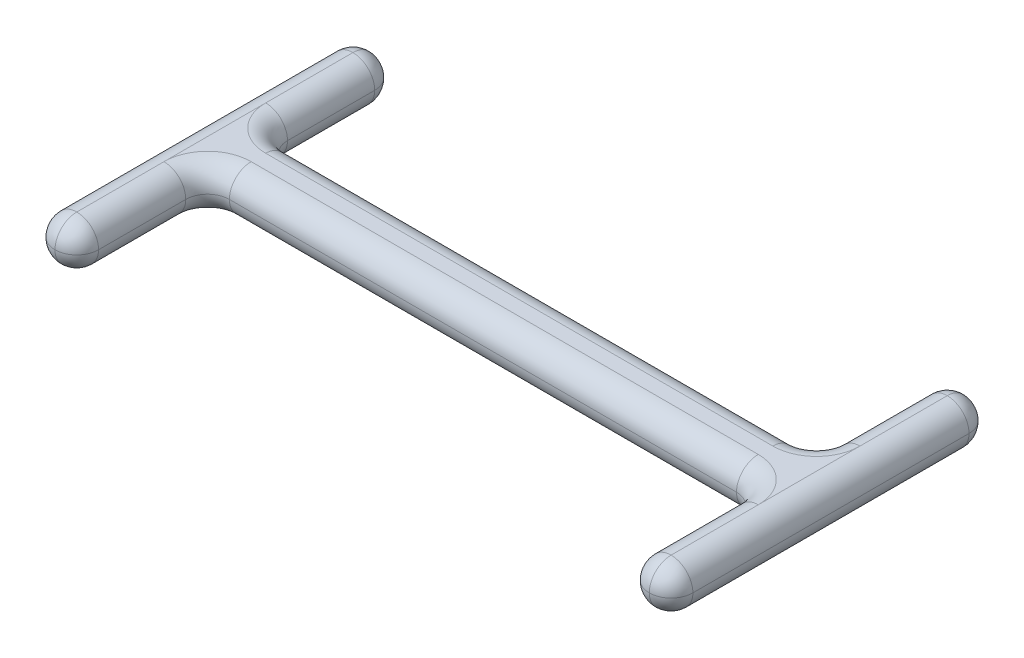
SolidWorks part; units mm, degrees
ref_plane "Front Plane" through (0, 0, 0) normal (0, 0, 1) x (1, 0, 0)
ref_plane "Top Plane" through (0, 0, 0) normal (0, 1, 0) x (1, 0, 0)
ref_plane "Right Plane" through (0, 0, 0) normal (1, 0, 0) x (0, 0, -1)
sketch "Sketch2" plane through (0, 0, 0) normal (0, 1, 0) x (1, 0, 0)
  line L0 (-54.865, 27.5) -> (-54.865, -27.5)
  line L1 (-54.865, -27.5) -> (-47.365, -27.5)
  line L2 (-47.365, -27.5) -> (-47.365, -5)
  line L3 (-47.365, -5) -> (47.365, -5)
  line L6 (0, 21.8993) -> (0, 0) construction
  line L7 (-48.8931, 0) -> (-54.865, 0) construction
  line L8 (47.365, -27.5) -> (47.365, -5)
  line L9 (54.865, -27.5) -> (47.365, -27.5)
  line L10 (54.865, 27.5) -> (54.865, -27.5)
  line L11 (-47.365, 27.5) -> (-47.365, 5)
  line L12 (-54.865, 27.5) -> (-47.365, 27.5)
  line L13 (54.865, 27.5) -> (47.365, 27.5)
  line L14 (47.365, 27.5) -> (47.365, 5)
  line L15 (-47.365, 5) -> (47.365, 5)
  dimension "D1" = 55
  dimension "D2" = 94.73
  dimension "D3" = 7.5
  dimension "D4" = 10
extrude "Boss-Extrude1" add sketch "Sketch2" along normal blind 7.5
fillet "Fillet1" radius 3.75 24 edges at (0, 7.5, 5) (0, 0, 5) (0, 7.5, -5) (0, 0, -5) (-47.365, 3.75, 27.5) (-47.365, 7.5, 16.25) (-47.365, 0, 16.25) (-54.865, 3.75, -27.5) (-54.865, 7.5, 0) (-54.865, 3.75, 27.5) (-54.865, 0, 0) (-47.365, 7.5, -16.25) (-47.365, 3.75, -27.5) (-47.365, 0, -16.25) (47.365, 7.5, 16.25) (47.365, 3.75, 27.5) (47.365, 0, 16.25) (47.365, 3.75, -27.5) (47.365, 7.5, -16.25) (47.365, 0, -16.25) (54.865, 3.75, 27.5) (54.865, 7.5, 0) (54.865, 3.75, -27.5) (54.865, 0, 0)
fillet "Fillet2" radius 3.75 16 edges at (-48.4633, 6.4017, -26.4017) (-48.4633, 1.0983, -26.4017) (-53.7667, 6.4017, 26.4017) (-53.7667, 1.0983, 26.4017) (48.4633, 1.0983, 26.4017) (48.4633, 6.4017, 26.4017) (53.7667, 1.0983, -26.4017) (53.7667, 6.4017, -26.4017) (-53.7667, 6.4017, -26.4017) (-53.7667, 1.0983, -26.4017) (-48.4633, 6.4017, 26.4017) (-48.4633, 1.0983, 26.4017) (53.7667, 1.0983, 26.4017) (53.7667, 6.4017, 26.4017) (48.4633, 1.0983, -26.4017) (48.4633, 6.4017, -26.4017)
